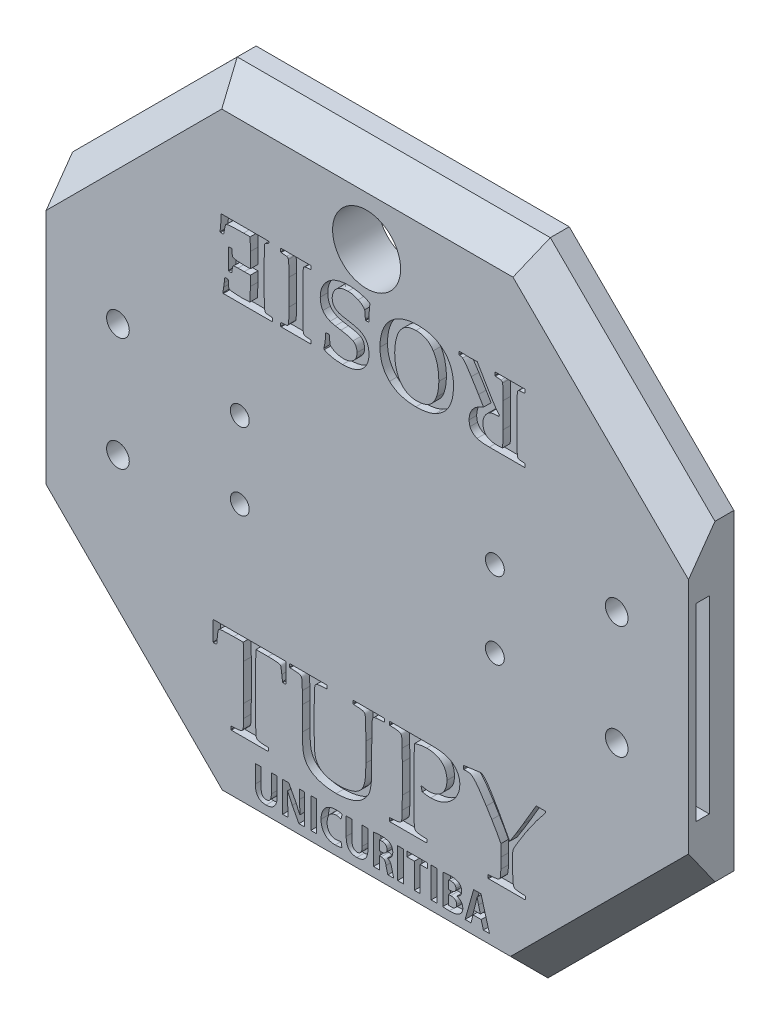
SolidWorks part; units mm, degrees
other "Marcação1"
sketch "Esboço6" plane through (-87.7736, -89.6425, -3) normal (-0.1034, -0.9882, -0.1129) x (0.9225, -0.1377, 0.3606)
ref_plane "Plano frontal" through (0, 0, 0) normal (0, 0, 1) x (1, 0, 0)
ref_plane "Plano superior" through (0, 0, 0) normal (0, 1, 0) x (1, 0, 0)
ref_plane "Plano direito" through (0, 0, 0) normal (1, 0, 0) x (0, 0, -1)
sketch "Esboço1" plane through (0, 0, 0) normal (0, 0, 1) x (1, 0, 0)
  line L56 (43.5631, -85.8021) -> (87.7643, -41.6735)
  line L57 (87.7643, -41.6735) -> (87.7643, 40.964)
  line L59 (44.1931, 84.1979) -> (-38.6632, 84.1929)
  line L60 (-38.6632, 84.1929) -> (-82.2357, 40.6256)
  line L61 (-82.2357, 40.6256) -> (-82.2357, -42.0102)
  line L63 (-38.5157, -85.8021) -> (43.5631, -85.8021)
  line L64 (-38.5157, -85.8021) -> (43.5631, -85.8021) construction
  line L65 (44.1931, 84.1979) -> (87.7643, 40.964)
  line L66 (43.5631, -85.8021) -> (87.7643, -41.6735) construction
  line L67 (-82.2357, -42.0102) -> (-38.5157, -85.8021)
  circle A5 centre (68.7643, 14.1979) radius 3
  circle A6 centre (68.7643, -15.8021) radius 3
  circle A7 centre (-63.2357, 14.1979) radius 3
  circle A8 centre (-63.2357, -15.8021) radius 3
  dimension "D1" = 19
  dimension "D2" = 19
  dimension "D4" = 30
  dimension "D6" = 19
  dimension "D3" = 70
  dimension "D5" = 30
  dimension "D7" = 70
extrude "Ressalto-extrusão1" add sketch "Esboço1" along normal blind 12
sketch "Esboço11" plane through (0, 0, 12) normal (0, 0, 1) x (1, 0, 0)
  line L0 (-38.5157, -85.8021) -> (43.5631, -85.8021) construction
  line L1 (87.7643, -41.6735) -> (87.7643, 40.964) construction
  circle A0 centre (-30.9844, 9.3479) radius 2.5
  circle A1 centre (-30.9844, -10.9521) radius 2.5
  circle A2 centre (36.5143, 8.9186) radius 2.5
  circle A3 centre (36.5143, -11.3814) radius 2.5
  dimension "D1" = 5
  dimension "D2" = 5
  dimension "D3" = 5
  dimension "D4" = 5
  dimension "D9" = 51.25
  dimension "D5" = 20.3
  dimension "D6" = 20.3
  dimension "D7" = 67.5
  dimension "D8" = 74.85
extrude "Corte-extrusão5" cut sketch "Esboço11" against normal through all
sketch "Esboço8" plane through (0, 0, 12) normal (0, 0, 1) x (1, 0, 0)
  line L0 (-80.3225, -63.9062) -> (92.2264, -63.9062) construction
  text T0 "TUPY" font "Palatino Linotype" height 23
extrude "Corte-extrusão3" cut sketch "Esboço8" against normal blind 2
sketch "Esboço9" plane through (0, 0, 12) normal (0, 0, 1) x (1, 0, 0)
  line L0 (-85.8316, 53.1216) -> (94.1684, 53.1238) construction
  line L1 (-52.8103, -76.3689) -> (60.5398, -76.3689) construction
  text T0 "ROSIE" font "Palatino Linotype" height 18
  text T1 "UNICURITIBA" font "@Adobe Gothic Std B" height 8
extrude "Corte-extrusão4" cut sketch "Esboço9" against normal blind 2
fillet "Chanfro1" radius 7 3 edges at (-60.3757, -63.9062, 12) (2.5237, -85.8021, 12) (65.6637, -63.7378, 12) type face fillet profile chamfer first side face at (-3.0804, 44.1844, 12) second side face at (2.5237, -85.8021, 6) second side face at (65.6637, -63.7378, 6) second side face at (-60.3757, -63.9062, 6)
fillet "Chanfro4" radius 7 3 edges at (65.9787, 62.5809, 12) (2.7649, 84.1954, 12) (-60.4494, 62.4093, 12) type face fillet profile chamfer first side face at (-3.0804, 44.1844, 12) second side face at (-60.4494, 62.4093, 6) second side face at (2.7649, 84.1954, 6) second side face at (65.9787, 62.5809, 6)
sketch "Esboço14" plane through (-82.2357, 0, 0) normal (-1, 0, 0) x (0, 0, 1)
  line L1 (6.5, 24.3056) -> (10, 24.3056)
  line L2 (10, 24.3056) -> (10, -25.6944)
  line L3 (10, -25.6944) -> (6.5, -25.6944)
  line L4 (6.5, -25.6944) -> (6.5, 24.3056)
  line L5 (12, 30.7267) -> (12, -32.1026) construction
  line L10 (5, 40.6256) -> (0, 40.6256) construction
  dimension "D1" = 2
  dimension "D2" = 3.5
  dimension "D3" = 16.32
  dimension "50" = 50
extrude "Corte-extrusão6" cut sketch "Esboço14" against normal blind 5
sketch "Esboço15" plane through (87.7643, 0, 0) normal (1, 0, 0) x (0, 0, -1)
  line L0 (-10, 24.644) -> (-6.5, 24.644)
  line L1 (-6.5, 24.644) -> (-6.5, -25.356)
  line L2 (-6.5, -25.356) -> (-10, -25.356)
  line L3 (-10, -25.356) -> (-10, 24.644)
  line L4 (-12, -31.7821) -> (-12, 31.1027) construction
  line L6 (-5, 40.964) -> (0, 40.964) construction
  dimension "D1" = 2
  dimension "D2" = 50
  dimension "D3" = 3.5
  dimension "D4" = 16.32
extrude "Corte-extrusão7" cut sketch "Esboço15" against normal blind 5
sketch "Esboço16" plane through (0, 0, 12) normal (0, 0, 1) x (1, 0, 0)
  line L2 (-38.6632, 84.1929) -> (44.1931, 84.1979) construction
  circle A0 centre (2.5715, 64.1954) radius 9
  dimension "D1" = 18
  dimension "D2" = 20
extrude "Corte-extrusão8" cut sketch "Esboço16" against normal through all
